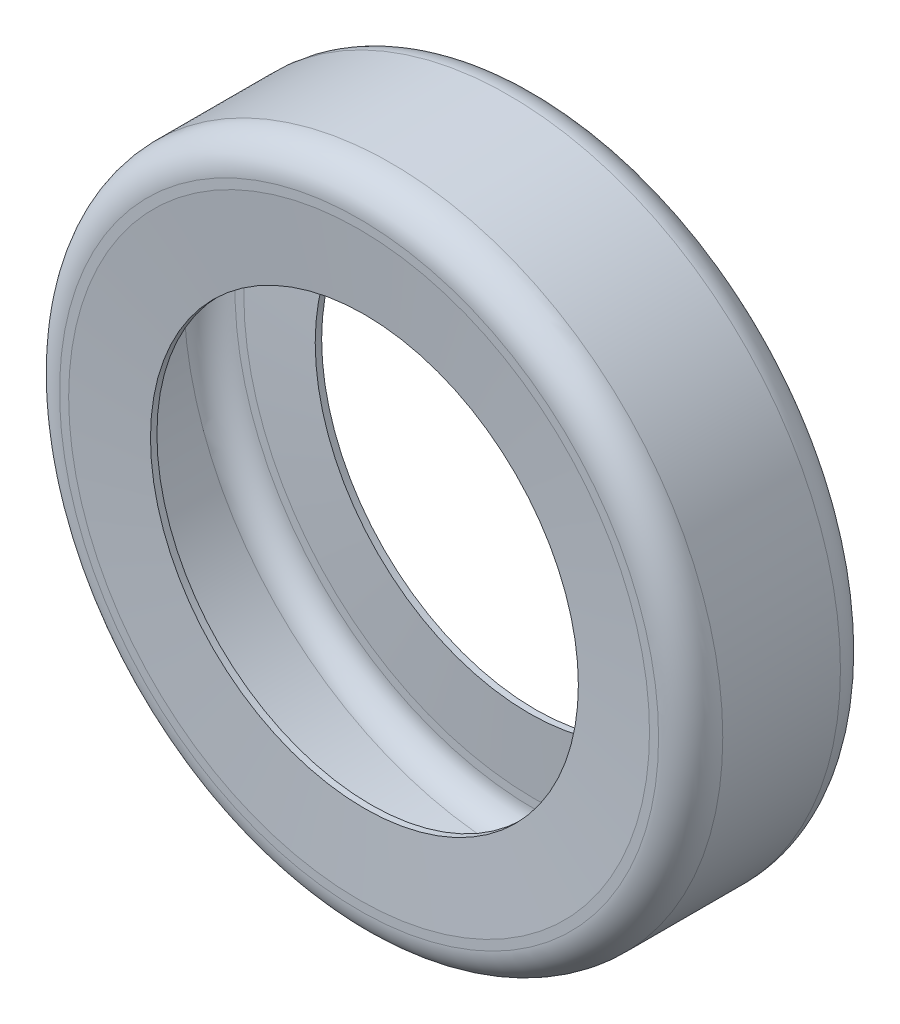
SolidWorks part; units mm, degrees
material "聚亚安酯(11671)"
ref_plane "前视基准面" through (0, 0, 0) normal (0, 0, 1) x (1, 0, 0)
ref_plane "上视基准面" through (0, 0, 0) normal (0, 1, 0) x (1, 0, 0)
ref_plane "右视基准面" through (0, 0, 0) normal (1, 0, 0) x (0, 0, -1)
sketch "草图1" plane through (0, 0, 0) normal (0, 0, 1) x (1, 0, 0)
  circle A0 centre (0, 0) radius 100
  circle A1 centre (0, 0) radius 175
  dimension "D1" = 350
  dimension "D2" = 200
extrude "凸台-拉伸1" add sketch "草图1" along normal blind 85
chamfer "倒角1" distance 2.5 angle 86 1 edges at (100, 0, 85) first distance on face at (100, 0, 85)
chamfer "倒角2" distance 2.5 angle 86 1 edges at (100, 0, 0) first distance on face at (100, 0, 82.5)
fillet "圆角1" radius 20 2 edges at (175, 0, 0) (175, 0, 85)
sketch "草图4" plane through (0, 0, 0) normal (0, 0, -1) x (-1, 0, 0)
  circle A0 centre (0, 0) radius 155
  circle A1 centre (0, 0) radius 243.9676
extrude "切除-拉伸3" cut sketch "草图4" against normal blind 156
fillet "圆角2" radius 15 2 edges at (-155, 0, 0) (-155, 0, 85)
shell "抽壳2" thickness 3 removed face at (100, 0, 2.5)
